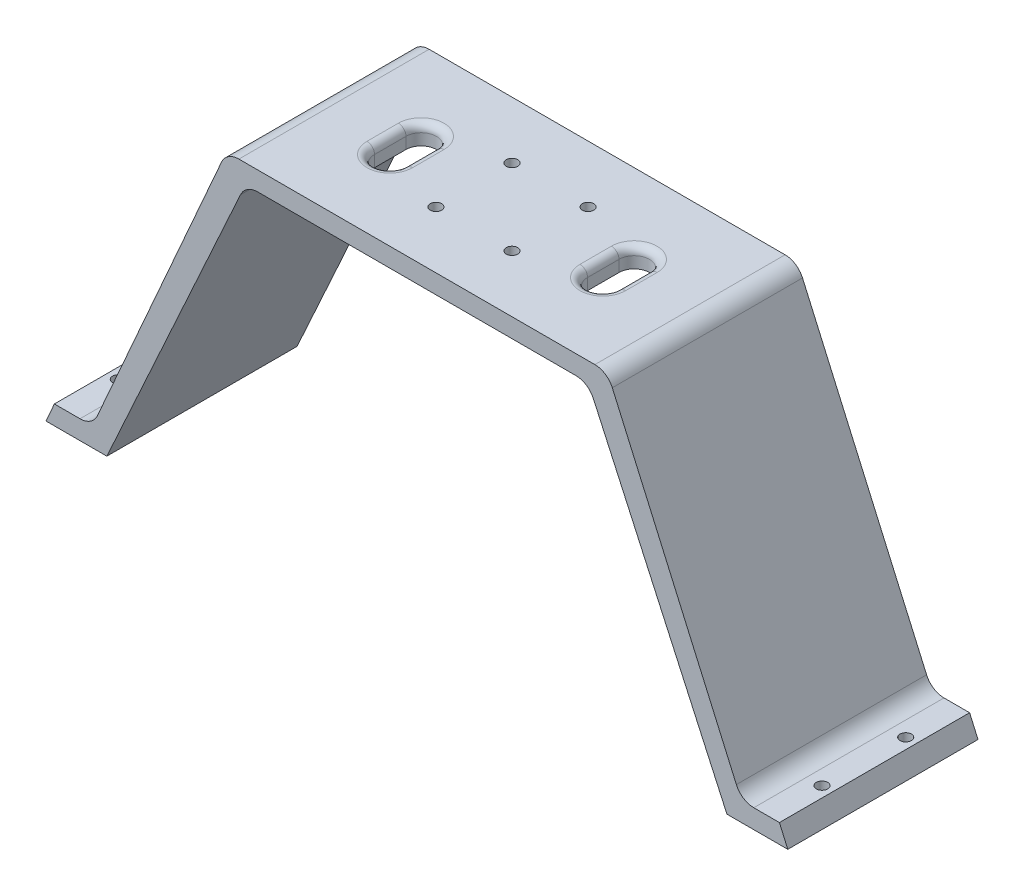
SolidWorks part; units mm, degrees
ref_plane "Front Plane" through (0, 0, 0) normal (0, 0, 1) x (1, 0, 0)
ref_plane "Top Plane" through (0, 0, 0) normal (0, 1, 0) x (1, 0, 0)
ref_plane "Right Plane" through (0, 0, 0) normal (1, 0, 0) x (0, 0, -1)
sketch "Sketch1" plane through (0, 0, 0) normal (0, 0, 1) x (1, 0, 0)
  line L0 (-87.5, 0) -> (87.5, 0)
  line L1 (-87.5, 0) -> (-50.05, 85)
  line L2 (-50.05, 85) -> (50.05, 85)
  line L3 (50.05, 85) -> (87.5, 0)
  point P4 (0, 0)
  dimension "D1" = 175
  dimension "D2" = 100.1
  dimension "D3" = 50.05
  dimension "D4" = 85
extrude "Boss-Extrude2" add sketch "Sketch1" along normal blind 50 contours L1 L2 L3 L0
sketch "Sketch3" plane through (0, 0, 50) normal (0, 0, 1) x (1, 0, 0)
  line L0 (-81.5, 0) -> (81.5, 0)
  line L1 (-87.5, 0) -> (87.5, 0) construction
  line L2 (81.5, 0) -> (45.05, 80)
  line L3 (45.05, 80) -> (-45.05, 80)
  line L4 (-45.05, 80) -> (-81.5, 0)
  line L5 (-50.05, 85) -> (50.05, 85) construction
  dimension "D1" = 163
  dimension "D2" = 6
  dimension "D3" = 90.1
  dimension "D4" = 45.05
  dimension "D5" = 5
extrude "Cut-Extrude1" cut sketch "Sketch3" against normal blind 50
fillet "Fillet1" radius 5 2 edges at (45.05, 80, 25) (-45.05, 80, 25)
sketch "Sketch5" plane through (73.2758, 32.2845, 0) normal (0.9151, 0.4032, 0) x (0, 0, -1)
  line L0 (0, 57.6053) -> (0, -35.2791) construction
  line L1 (-50, -35.2791) -> (0, -35.2791)
  line L2 (-50, -35.2791) -> (-50, -29.8151)
  line L3 (-50, -29.8151) -> (0, -29.8151)
  line L4 (0, -35.2791) -> (0, -29.8151)
  dimension "D1" = 5.464
sketch "Sketch8" plane through (0, 0, 0) normal (0, 1, 0) x (1, 0, 0)
  line L0 (93.2771, -25.8796) -> (149.3121, -25.8796)
  point P2 (0, 0)
sketch "Sketch9" plane through (0, 0, 0) normal (0, 1, 0) x (1, 0, 0)
  line L0 (-93.9767, -25.7952) -> (-133.9417, -25.7952)
sketch "Sketch10" plane through (-73.2758, 32.2845, 0) normal (-0.9151, 0.4032, 0) x (0, 0, 1)
  line L0 (0, -35.2791) -> (0, 57.6053) construction
  line L1 (50, -35.2791) -> (0, -35.2791)
  line L2 (50, -35.2791) -> (50, -29.8191)
  line L3 (50, -29.8191) -> (0, -29.8191)
  line L4 (0, -35.2791) -> (0, -29.8191)
  dimension "D1" = 5.46
extrude "Boss-Extrude4" add sketch "Sketch10" along direction (-1, 0, 0) on the side of the normal blind 10
extrude "Boss-Extrude5" add sketch "Sketch5" along direction (1, 0, 0) on the side of the normal blind 10 contours L3 L4 L1 L2
sketch "Sketch11" plane through (0, 4.9965, 0) normal (0, 1, 0) x (1, 0, 0)
  line L0 (-97.5, 0) -> (-97.5, -50) construction
  line L1 (-95.2986, -50) -> (-85.2986, -50) construction
  circle A0 centre (-92.5, -14) radius 1.5
  circle A1 centre (-92.5, -36) radius 1.5
  dimension "D1" = 22
  dimension "D2" = 5
  dimension "D3" = 14
extrude "Cut-Extrude2" cut sketch "Sketch11" against normal blind 10
sketch "Sketch12" plane through (0, 5.0002, 0) normal (0, 1, 0) x (1, 0, 0)
  line L0 (97.5, -50) -> (97.5, 0) construction
  line L1 (95.297, -50) -> (85.297, -50) construction
  circle A0 centre (92.5, -14) radius 1.5
  circle A1 centre (92.5, -36) radius 1.5
  dimension "D1" = 22
  dimension "D2" = 5
  dimension "D3" = 14
extrude "Cut-Extrude3" cut sketch "Sketch12" against normal blind 10
fillet "Fillet2" radius 5 2 edges at (85.297, 5.0002, 25) (-85.2986, 4.9965, 25)
fillet "Fillet3" radius 5 2 edges at (50.05, 85, 25) (-50.05, 85, 25)
sketch "Sketch13" plane through (0, 85, 0) normal (0, 1, 0) x (1, 0, 0)
  line L1 (-46.7892, 0) -> (-46.7892, -50) construction
  line L3 (-46.7892, 0) -> (46.7892, 0) construction
  line L4 (-46.7892, -50) -> (46.7892, -50) construction
  circle A0 centre (-9.9992, -15) radius 1.5
  circle A1 centre (10.0008, -15) radius 1.5
  circle A2 centre (-9.9992, -35) radius 1.5
  circle A3 centre (10.0008, -35) radius 1.5
  dimension "D1" = 20
  dimension "D2" = 20
  dimension "D3" = 20
  dimension "D4" = 20
  dimension "D5" = 36.79
  dimension "D6" = 15
extrude "Cut-Extrude5" cut sketch "Sketch13" against normal blind 10
sketch "Sketch14" plane through (0, 80, 0) normal (0, -1, 0) x (1, 0, 0)
  circle A0 centre (-9.9992, 35) radius 3
  circle A1 centre (-9.9992, 15) radius 3
  circle A2 centre (10.0008, 35) radius 3
  circle A3 centre (10.0008, 15) radius 3
extrude "Cut-Extrude6" cut sketch "Sketch14" against normal blind 2.5
sketch "Sketch15" plane through (0, 85, 0) normal (0, 1, 0) x (1, 0, 0)
  line L0 (-27.9992, -20.87) -> (-27.9992, -29.13) construction
  line L1 (-23.9992, -20.87) -> (-23.9992, -29.13)
  line L2 (-31.9992, -20.87) -> (-31.9992, -29.13)
  line L3 (28.0008, -20.87) -> (28.0008, -29.13) construction
  line L4 (32.0008, -20.87) -> (32.0008, -29.13)
  line L5 (24.0008, -20.87) -> (24.0008, -29.13)
  line L6 (-46.7892, 0) -> (46.7892, 0) construction
  line L7 (-46.7892, -50) -> (46.7892, -50) construction
  arc A0 (-23.9992, -20.87) -> (-31.9992, -20.87) centre (-27.9992, -20.87) ccw
  arc A1 (-31.9992, -29.13) -> (-23.9992, -29.13) centre (-27.9992, -29.13) ccw
  arc A2 (32.0008, -20.87) -> (24.0008, -20.87) centre (28.0008, -20.87) ccw
  arc A3 (24.0008, -29.13) -> (32.0008, -29.13) centre (28.0008, -29.13) ccw
  circle A4 centre (-9.9992, -15) radius 1.5 construction
  circle A5 centre (10.0008, -15) radius 1.5 construction
  point P2 (-27.9992, -25)
  point P7 (28.0008, -25)
  point P14 (28.0008, -16.87)
  dimension "D5" = 20.87
  dimension "D1" = 4
  dimension "D2" = 4
  dimension "D3" = 18
  dimension "D4" = 18
  dimension "D6" = 20.87
  dimension "D7" = 20.87
  dimension "D8" = 20.87
extrude "Cut-Extrude8" cut sketch "Sketch15" against normal blind 8.5
fillet "Fillet5" radius 2 8 edges at (-27.9992, 85, 33.13) (-23.9992, 85, 25) (-31.9992, 85, 25) (-27.9992, 85, 16.87) (28.0008, 85, 16.87) (32.0008, 85, 25) (24.0008, 85, 25) (28.0008, 85, 33.13)
